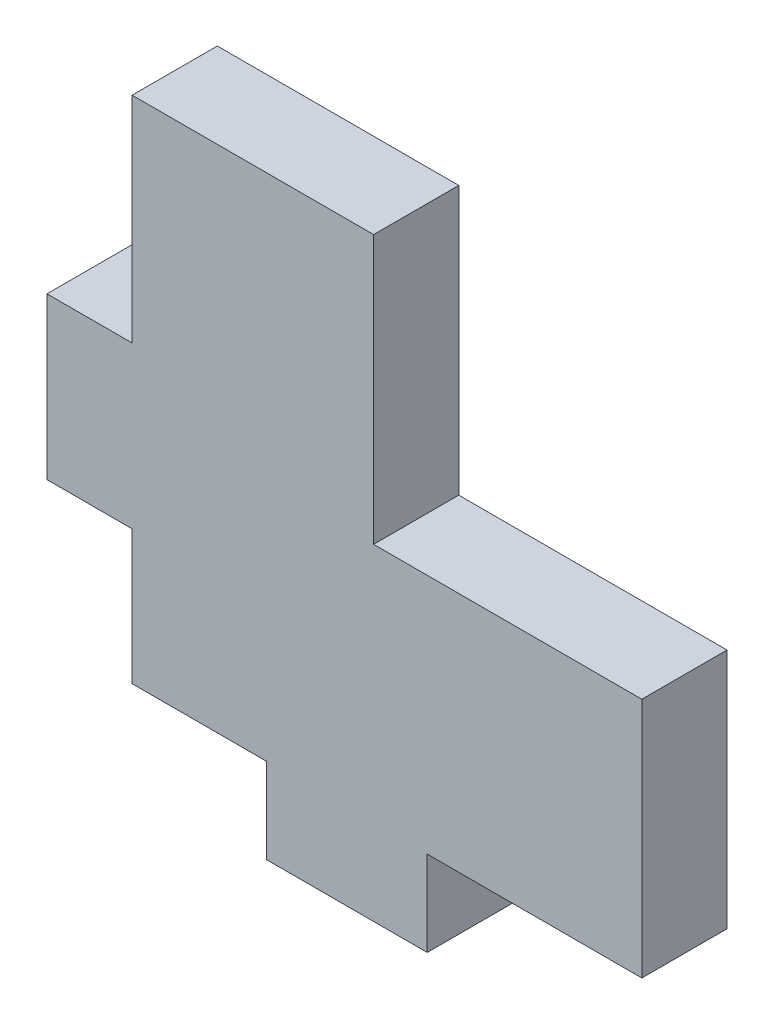
SolidWorks part; units mm, degrees
ref_plane "Front Plane" through (0, 0, 0) normal (0, 0, 1) x (1, 0, 0)
ref_plane "Top Plane" through (0, 0, 0) normal (0, 1, 0) x (1, 0, 0)
ref_plane "Right Plane" through (0, 0, 0) normal (1, 0, 0) x (0, 0, -1)
sketch "Sketch1" plane through (0, 0, 0) normal (0, 0, 1) x (1, 0, 0)
  line L0 (0, 0) -> (5, 0)
  line L1 (5, 0) -> (5, -3.175)
  line L2 (5, -3.175) -> (11, -3.175)
  line L3 (11, -3.175) -> (11, 0)
  line L4 (11, 0) -> (19, 0)
  line L5 (19, 0) -> (19, 9)
  line L6 (19, 9) -> (9, 9)
  line L7 (9, 9) -> (9, 19)
  line L8 (9, 19) -> (0, 19)
  line L9 (0, 19) -> (0, 11)
  line L10 (0, 11) -> (-3.175, 11)
  line L11 (-3.175, 11) -> (-3.175, 5)
  line L12 (-3.175, 5) -> (0, 5)
  line L13 (0, 5) -> (0, 0)
  dimension "D1" = 10
  dimension "D2" = 9
  dimension "D3" = 6
  dimension "D4" = 3.175
  dimension "D5" = 5
extrude "Boss-Extrude1" add sketch "Sketch1" along normal mid plane 3.175
